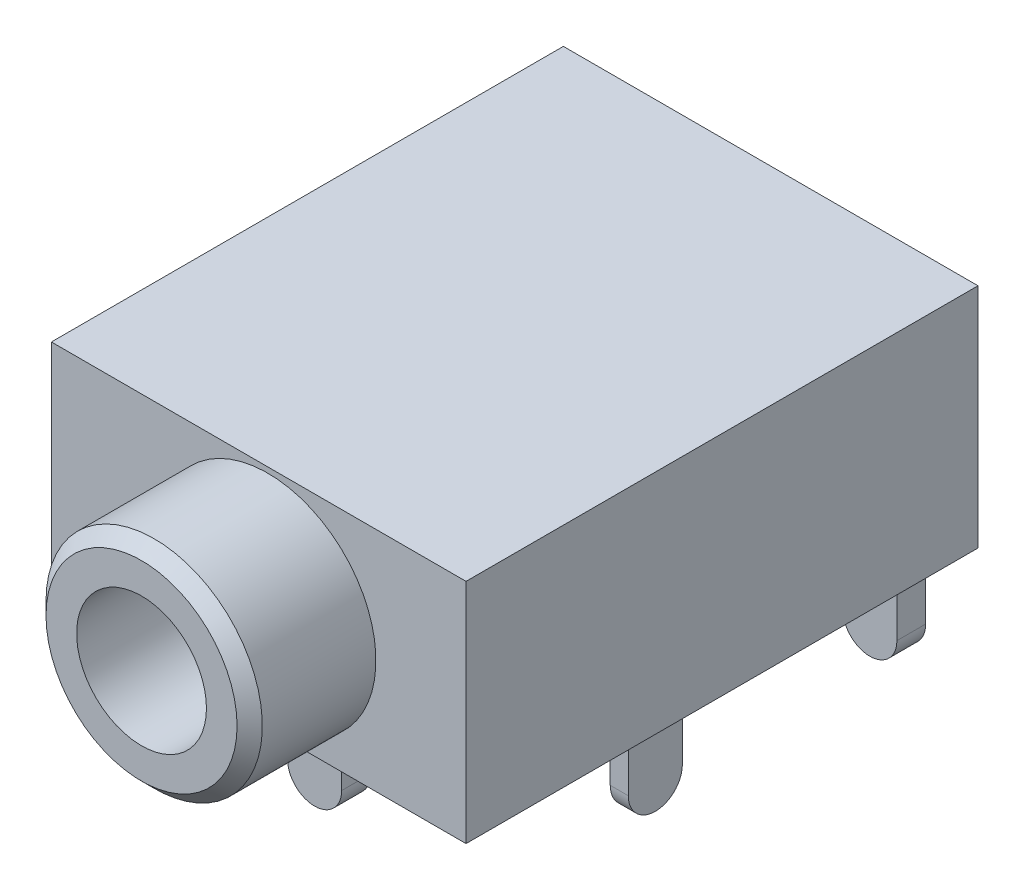
SolidWorks part; units mm, degrees
ref_plane "Front" through (0, 0, 0) normal (0, 0, 1) x (1, 0, 0)
ref_plane "Top" through (0, 0, 0) normal (0, 1, 0) x (1, 0, 0)
ref_plane "Right" through (0, 0, 0) normal (1, 0, 0) x (0, 0, -1)
sketch "Sketch1" plane through (0, 0, 0) normal (0, 1, 0) x (1, 0, 0)
  line L1 (0, 0) -> (11.5, 0)
  line L2 (0, 0) -> (0, 14.2)
  line L3 (0, 14.2) -> (11.5, 14.2)
  line L4 (11.5, 0) -> (11.5, 14.2)
  dimension "D1" = 14.2
  dimension "D2" = 11.5
extrude "Boss-Extrude1" add sketch "Sketch1" along normal blind 6.3
sketch "Sketch2" plane through (0, 0, 0) normal (0, 0, 1) x (1, 0, 0)
  line L0 (0, 3.15) -> (11.5, 3.15) construction
  line L1 (0, 6.3) -> (0, 0) construction
  line L2 (11.5, 6.3) -> (11.5, 0) construction
  circle A0 centre (6, 3.15) radius 3
  circle A1 centre (6, 3.15) radius 1.8
  dimension "D1" = 6
  dimension "D2" = 5.5
  dimension "D3" = 3.6
extrude "Boss-Extrude2" add sketch "Sketch2" along normal blind 3.5
sketch "Sketch3" plane through (0, 0, 0) normal (0, -1, 0) x (1, 0, 0)
  line L0 (6, 0) -> (6, -14.2) construction
  line L1 (5.25, -2.1) -> (6.75, -2.1)
  line L2 (5.25, -2.1) -> (5.25, -1.3)
  line L3 (5.25, -1.3) -> (6.75, -1.3)
  line L4 (6.75, -2.1) -> (6.75, -1.3)
  line L5 (3, -9.35) -> (3.8, -9.35)
  line L6 (3, -9.35) -> (3, -7.85)
  line L7 (3, -7.85) -> (3.8, -7.85)
  line L8 (3.8, -9.35) -> (3.8, -7.85)
  line L9 (0.55, -10.35) -> (1.05, -10.35)
  line L10 (0.55, -10.35) -> (0.55, -8.85)
  line L11 (0.55, -8.85) -> (1.05, -8.85)
  line L12 (1.05, -10.35) -> (1.05, -8.85)
  line L13 (10.35, -6.65) -> (10.85, -6.65)
  line L14 (10.35, -6.65) -> (10.35, -5.15)
  line L15 (10.35, -5.15) -> (10.85, -5.15)
  line L16 (10.85, -6.65) -> (10.85, -5.15)
  line L17 (9.35, -13.4) -> (10.85, -13.4)
  line L18 (9.35, -13.4) -> (9.35, -12.6)
  line L19 (9.35, -12.6) -> (10.85, -12.6)
  line L20 (10.85, -13.4) -> (10.85, -12.6)
  line L21 (9, 0) -> (3, 0) construction
  line L22 (11.5, -14.2) -> (0, -14.2) construction
  line L23 (5.25, -1.7) -> (6.75, -1.7) construction
  line L24 (6, -2.1) -> (6, -1.3) construction
  line L25 (3.4, -9.35) -> (3.4, -7.85) construction
  line L26 (3, -8.6) -> (3.8, -8.6) construction
  line L27 (0.8, -10.35) -> (0.8, -8.85) construction
  line L28 (0.55, -9.6) -> (1.05, -9.6) construction
  line L29 (10.1, -13.4) -> (10.1, -12.6) construction
  line L30 (10.85, -13) -> (9.35, -13) construction
  line L31 (10.6, -6.65) -> (10.6, -5.15) construction
  line L32 (10.85, -5.9) -> (10.35, -5.9) construction
  line L33 (0, 0) -> (11.5, 0) construction
  dimension "D1" = 1.5
  dimension "D2" = 1.5
  dimension "D3" = 1.5
  dimension "D4" = 1.5
  dimension "D5" = 1.5
  dimension "D6" = 0.5
  dimension "D7" = 0.5
  dimension "D8" = 0.8
  dimension "D9" = 0.8
  dimension "D10" = 0.8
  dimension "D11" = 1.7
  dimension "D12" = 4.2
  dimension "D13" = 8.6
  dimension "D14" = 1
  dimension "D15" = 2.6
  dimension "D16" = 5.2
  dimension "D17" = 4.1
  dimension "D18" = 4.6
  dimension "D19" = 13
extrude "Boss-Extrude3" add sketch "Sketch3" along normal blind 2.5 separate body
fillet "Fillet1" radius 0.75 2 edges at (6.75, -2.5, -1.7) (5.25, -2.5, -1.7)
fillet "Fillet2" radius 0.75 2 edges at (10.6, -2.5, -6.65) (10.6, -2.5, -5.15)
fillet "Fillet3" radius 0.75 2 edges at (3.4, -2.5, -9.35) (3.4, -2.5, -7.85)
fillet "Fillet4" radius 0.75 2 edges at (0.8, -2.5, -10.35) (0.8, -2.5, -8.85)
fillet "Fillet5" radius 0.75 2 edges at (10.85, -2.5, -13) (9.35, -2.5, -13)
chamfer "Chamfer1" distance 0.35 angle 45 1 edges at (9, 3.15, 3.5)
equation "\"D2@Sketch3\"=\"D1@Sketch3\""
equation "\"D3@Sketch3\"=\"D1@Sketch3\""
equation "\"D4@Sketch3\"=\"D1@Sketch3\""
equation "\"D5@Sketch3\"=\"D1@Sketch3\""
equation "\"D7@Sketch3\"=\"D6@Sketch3\""
equation "\"D9@Sketch3\"=\"D8@Sketch3\""
equation "\"D10@Sketch3\"=\"D8@Sketch3\""
